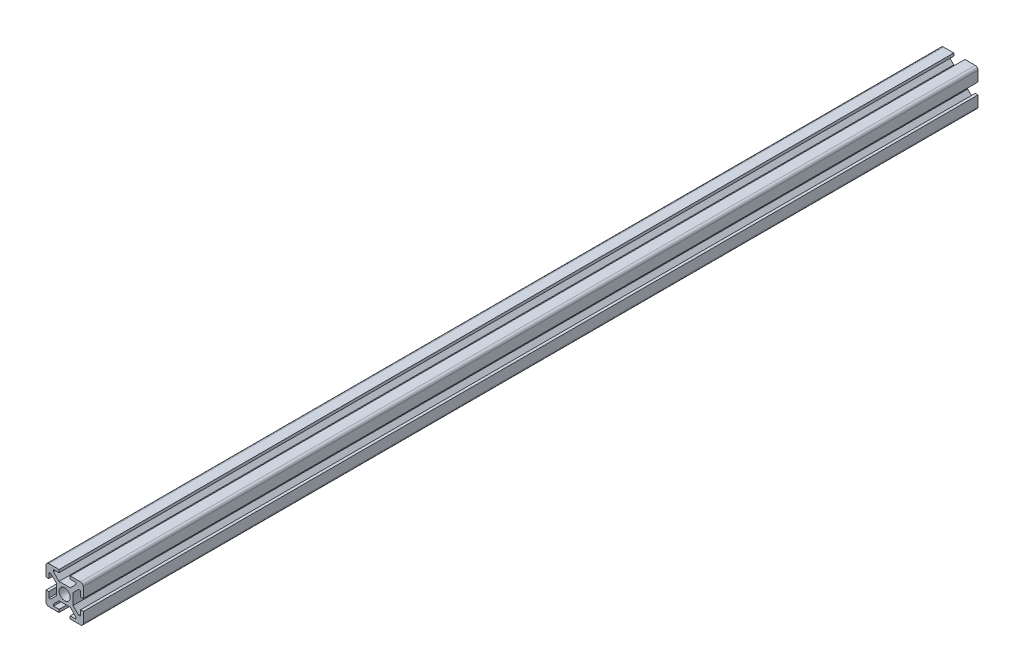
SolidWorks part; units mm, degrees
ref_plane "Plan de face" through (0, 0, 0) normal (0, 0, 1) x (1, 0, 0)
ref_plane "Plan de dessus" through (0, 0, 0) normal (0, 1, 0) x (1, 0, 0)
ref_plane "Plan de droite" through (0, 0, 0) normal (1, 0, 0) x (0, 0, -1)
sketch "Esquisse1" plane through (0, 0, 0) normal (0, 0, 1) x (1, 0, 0)
  line L0 (-10, 10) -> (10, -10) construction
  line L1 (-10, 10) -> (10, 10)
  line L2 (-10, 10) -> (-10, -10)
  line L3 (-10, -10) -> (10, -10)
  line L4 (10, 10) -> (10, -10)
  dimension "D1" = 20
extrude "Extrusion1" add sketch "Esquisse1" along normal mid plane 480
fillet "Congé1" radius 1.5 4 edges at (-10, -10, 0) (10, -10, 0) (-10, 10, 0) (10, 10, 0)
sketch "Esquisse2" plane through (0, 0, -240) normal (0, 0, -1) x (-1, 0, 0)
  line L0 (-10, 3) -> (-10, -3)
  line L1 (-10, -8.5) -> (-10, 8.5) construction
  line L2 (-10, -3) -> (-8.5, -3)
  line L3 (-8.5, -3) -> (-8.5, -6)
  line L4 (-8.5, 6) -> (-7.5, 6)
  line L5 (-4.5, -3) -> (-4.5, 3)
  line L6 (-7.5, 6) -> (-4.5, 3)
  line L7 (-8.5, 6) -> (-8.5, 3)
  line L8 (-8.5, 3) -> (-10, 3)
  line L9 (0, 0) -> (-10, 0) construction
  line L10 (-8.5, -6) -> (-7.5, -6)
  line L11 (-7.5, -6) -> (-4.5, -3)
  point P4 (-10, 0)
  dimension "D1" = 6
  dimension "D2" = 12
  dimension "D3" = 1.5
  dimension "D4" = 5.5
  dimension "D5" = 135
extrude "Enlèv. mat.-Extru.1" cut sketch "Esquisse2" against normal through all
ref_axis "Axe1" through (0, 0, 9.3338) along (0, 0, -1)
pattern_circular "Répétition circulaire1" count 4 over 360 about axis through (0, 0, 9.3338) along (0, 0, -1) of "Enlèv. mat.-Extru.1"
hole_wizard "Trou taraudé M6x1.01" positions "Esquisse4" profile "Esquisse5" tap size "M6x1.0" standard "Ansi Métrique"
sketch "Esquisse4" plane through (0, 0, -240) normal (0, 0, -1) x (-1, 0, 0)
  point P0 (0, 0)
sketch "Esquisse5" plane through (0, 0, -240) normal (1, 0, 0) x (0, 1, 0)
  line L0 (0, 0) -> (0, 31.5022)
  line L1 (0, 31.5022) -> (2.5, 30)
  line L2 (2.5, 30) -> (2.5, 24)
  line L3 (2.5, 24) -> (3, 24)
  line L4 (3, 24) -> (3, 0)
  line L5 (3, 0) -> (0, 0)
  line L10 (0, 31.5022) -> (-2.5, 30) construction
  line L11 (0, -6.35) -> (0, 107.95) construction
  dimension "Diamètre du trou pour taraudage" = 5
  dimension "Profondeur du trou pour taraudage" = 30
  dimension "Diamètre principal du filetage" = 6
  dimension "Profondeur du filetage" = 24
  dimension "Angle de pointe" = 118
mirror "Symétrie1" about plane through (0, 0, 0) normal (0, 0, 1) of "Trou taraudé M6x1.01"
